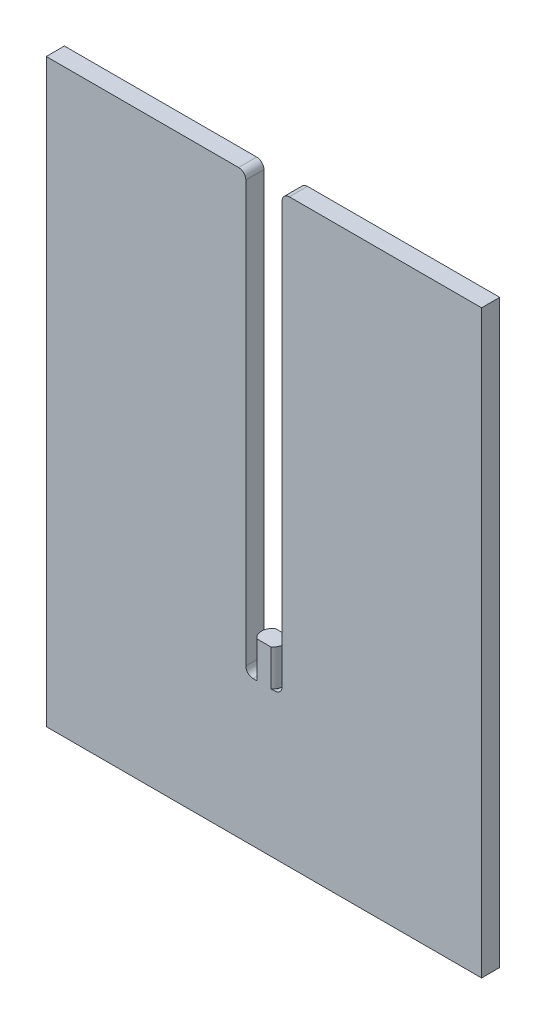
SolidWorks part; units mm, degrees
ref_plane "Front Plane" through (0, 0, 0) normal (0, 0, 1) x (1, 0, 0)
ref_plane "Top Plane" through (0, 0, 0) normal (0, 1, 0) x (1, 0, 0)
ref_plane "Right Plane" through (0, 0, 0) normal (1, 0, 0) x (0, 0, -1)
sketch "Sketch1" plane through (0, 0, 0) normal (0, 0, 1) x (1, 0, 0)
  line L0 (-2.5, 40) -> (-2.5, -20)
  line L1 (-30, 40) -> (-2.5, 40)
  line L2 (-30, 40) -> (-30, -40)
  line L3 (-30, -40) -> (30, -40)
  line L4 (30, 40) -> (30, -40)
  line L5 (-30, 40) -> (30, -40) construction
  line L6 (-30, -40) -> (30, 40) construction
  line L7 (0, 0) -> (0, 62.4551) construction
  line L8 (-2.5, -20) -> (2.5, -20)
  line L9 (2.5, 40) -> (2.5, -20)
  line L10 (2.5, 40) -> (30, 40)
  point P0 (0, 0)
  point P12 (0, -20)
  dimension "D1" = 60
  dimension "D2" = 80
  dimension "D3" = 5
  dimension "D4" = 60
extrude "Boss-Extrude1" add sketch "Sketch1" along normal blind 2.5
fillet "Fillet1" radius 1 4 edges at (-2.5, -20, 1.25) (2.5, -20, 1.25) (-2.5, 40, 1.25) (2.5, 40, 1.25)
sketch "Sketch2" plane through (0, -20, 0) normal (0, 1, 0) x (1, 0, 0)
  line L0 (1.5, -1.25) -> (-1.5, -1.25) construction
  line L1 (1.5, -2.5) -> (1.5, 0) construction
  line L2 (-1.5, 0) -> (-1.5, -2.5) construction
  line L3 (0, 0) -> (0, -2.5) construction
  line L4 (1.5, 0) -> (-1.5, 0) construction
  line L5 (1.5, -2.5) -> (-1.5, -2.5) construction
  line L6 (-0.9579, 0) -> (0.9579, 0)
  line L7 (0.9579, -2.5) -> (-0.9579, -2.5)
  arc A0 (0.9579, -2.5) -> (0.9579, 0) centre (0, -1.25) ccw
  arc A1 (-0.9579, 0) -> (-0.9579, -2.5) centre (0, -1.25) ccw
  dimension "D1" = 3.1496
extrude "Boss-Extrude2" add sketch "Sketch2" along normal blind 5
